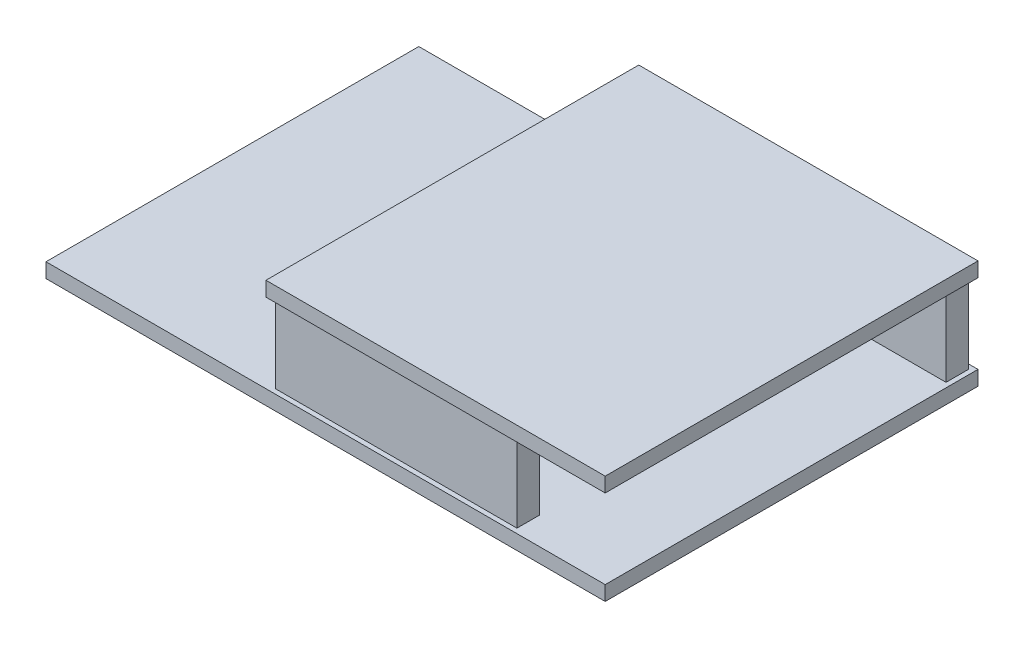
SolidWorks part; units mm, degrees
ref_plane "Front Plane" through (0, 0, 0) normal (0, 0, 1) x (1, 0, 0)
ref_plane "Top Plane" through (0, 0, 0) normal (0, 1, 0) x (1, 0, 0)
ref_plane "Right Plane" through (0, 0, 0) normal (1, 0, 0) x (0, 0, -1)
sketch "Sketch1" plane through (0, 0, 0) normal (0, 1, 0) x (1, 0, 0)
  line L1 (-30, -20) -> (30, -20)
  line L2 (-30, -20) -> (-30, 20)
  line L3 (-30, 20) -> (30, 20)
  line L4 (30, -20) -> (30, 20)
  line L5 (-30, -20) -> (30, 20) construction
  line L6 (-30, 20) -> (30, -20) construction
  point P0 (0, 0)
  dimension "D1" = 60
  dimension "D2" = 40
extrude "Boss-Extrude1" add sketch "Sketch1" along normal blind 1.57
sketch "Sketch2" plane through (0, 1.57, 0) normal (0, 1, 0) x (1, 0, 0)
  line L0 (-6.4, -20) -> (-6.4, 20) construction
  line L1 (29.49, 19.49) -> (3.58, 19.49)
  line L2 (29.49, 19.49) -> (29.49, 17.08)
  line L3 (29.49, 17.08) -> (3.58, 17.08)
  line L4 (3.58, 19.49) -> (3.58, 17.08)
  line L5 (20.02, -17.08) -> (-5.89, -17.08)
  line L6 (20.02, -17.08) -> (20.02, -19.49)
  line L7 (20.02, -19.49) -> (-5.89, -19.49)
  line L8 (-5.89, -17.08) -> (-5.89, -19.49)
  line L9 (-30, -20) -> (30, -20) construction
  line L10 (30, 20) -> (-30, 20) construction
  line L11 (30, -20) -> (30, 20) construction
  circle A0 centre (25, -15) radius 3.2 construction
  dimension "D6" = 6.4
  dimension "D1" = 2.41
  dimension "D2" = 2.41
  dimension "D3" = 25.91
  dimension "D4" = 25.91
  dimension "D5" = 36.4
  dimension "D7" = 5
  dimension "D8" = 5
  dimension "D9" = 0.51
  dimension "D10" = 0.51
  dimension "D11" = 0.51
  dimension "D12" = 0.51
extrude "Boss-Extrude2" add sketch "Sketch2" along normal blind 8.51
sketch "Sketch3" plane through (0, 10.08, 0) normal (0, 1, 0) x (1, 0, 0)
  line L0 (30, 20) -> (-30, 20) construction
  line L1 (30, -20) -> (-6.4, -20)
  line L2 (30, -20) -> (30, 20)
  line L3 (30, 20) -> (-6.4, 20)
  line L4 (-6.4, -20) -> (-6.4, 20)
  dimension "D1" = 36.4
extrude "Boss-Extrude3" add sketch "Sketch3" along normal blind 1.57
